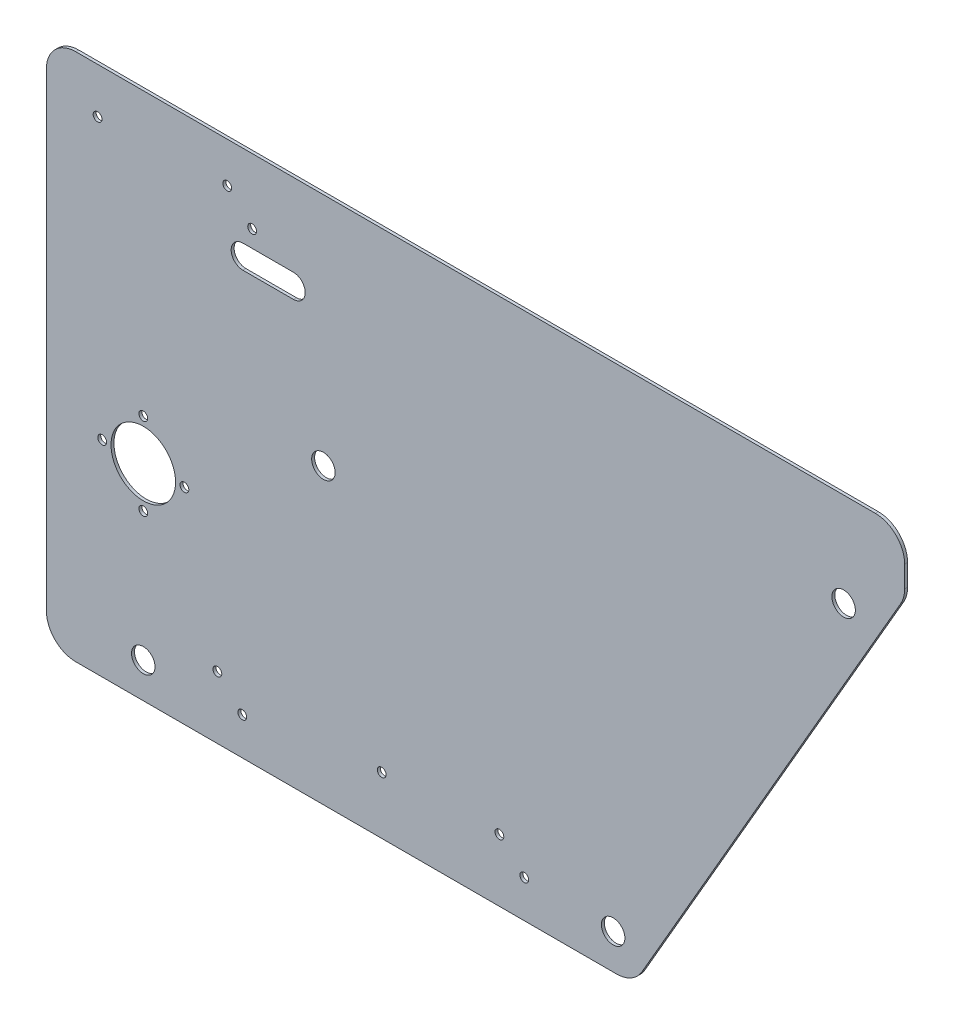
SolidWorks part; units mm, degrees
ref_plane "Front Plane" through (0, 0, 0) normal (0, 0, 1) x (1, 0, 0)
ref_plane "Top Plane" through (0, 0, 0) normal (0, 1, 0) x (1, 0, 0)
ref_plane "Right Plane" through (0, 0, 0) normal (1, 0, 0) x (0, 0, -1)
sketch "Sketch1" plane through (0, 0, 0) normal (0, 0, 1) x (1, 0, 0)
  line L0 (100, 80) -> (192.376, 80)
  line L1 (-100, -80) -> (100, -80)
  line L2 (-100, -80) -> (-100, 80)
  line L3 (-100, 80) -> (100, 80)
  line L4 (100, -80) -> (100, 80)
  line L5 (-100, -80) -> (100, 80) construction
  line L6 (-100, 80) -> (100, -80) construction
  line L7 (192.376, 80) -> (100, -80)
  line L8 (100, 80) -> (100, -80)
  line L10 (-100, 80) -> (192.376, 80)
  line L11 (-100, 80) -> (-100, 100)
  line L12 (-100, 100) -> (192.376, 100)
  line L13 (192.376, 80) -> (192.376, 100)
  point P0 (0, 0)
  dimension "D1" = 160
  dimension "D2" = 200
  dimension "D3" = 30
  dimension "D4" = 20
extrude "Boss-Extrude1" add sketch "Sketch1" along normal blind 1 contours L1 L4 L3 L2 | L7 L0 L4 | L11 L10 L13 L12 region at (0, 0, 0) region at (130.792, 26.6667, 0)
fillet "Fillet1" radius 10 5 edges at (100, -80, 0.5) (-100, -80, 0.5) (192.376, 100, 0.5) (-100, 100, 0.5) (192.376, 80, 0.5)
sketch "Sketch2" plane through (0, 0, 1) normal (0, 0, 1) x (1, 0, 0)
  line L0 (-90, -80) -> (94.2265, -80) construction
  line L1 (191.0363, 77.6795) -> (102.8868, -75) construction
  line L3 (-90, 100) -> (182.376, 100) construction
  line L4 (-33.0592, 68) -> (-15.8429, 68) construction
  line L7 (-100, -70) -> (-100, 90) construction
  line L9 (-33.0592, 72) -> (-15.8429, 72)
  line L10 (-33.0592, 64) -> (-15.8429, 64)
  circle A0 centre (93.0718, -68) radius 4
  circle A1 centre (171.5914, 68) radius 4
  circle A2 centre (-67, -10) radius 11
  circle A3 centre (-67, -68) radius 4
  circle A4 centre (-53, -10) radius 1.5
  circle A5 centre (-67, 4) radius 1.5
  circle A6 centre (-81, -10) radius 1.5
  circle A7 centre (-67, -24) radius 1.5
  circle A10 centre (-5.639, 20) radius 4
  arc A11 (-33.0592, 72) -> (-33.0592, 64) centre (-33.0592, 68) ccw
  arc A12 (-15.8429, 64) -> (-15.8429, 72) centre (-15.8429, 68) ccw
  circle A32 centre (62.7961, -67.2426) radius 1.5
  circle A33 centre (54.3108, -58.7574) radius 1.5
  circle A34 centre (-33.2742, -67.2426) radius 1.5
  circle A35 centre (-41.7595, -58.7574) radius 1.5
  circle A36 centre (14.2259, -60.5) radius 1.5
  circle A37 centre (-29.9152, 77.7574) radius 1.5
  circle A38 centre (-38.4005, 86.2426) radius 1.5
  circle A39 centre (-82.5763, 84.5) radius 1.5
  point P12 (-24.451, 68)
  point P36 (0, 0)
  point P38 (0, 0)
  point P39 (0, 0)
  point P42 (-5.639, 20)
  point P44 (0, 0)
  point P45 (0, 0)
  dimension "D3" = 8
  dimension "D4" = 8
  dimension "D9" = 22
  dimension "D10" = 8
  dimension "D12" = 3
  dimension "D13" = 3
  dimension "D14" = 3
  dimension "D15" = 3
  dimension "D16" = 14
  dimension "D20" = 4
  dimension "D22" = 8
  dimension "D23" = 3
  dimension "D1" = 12
  dimension "D2" = 12
  dimension "D5" = 32
  dimension "D6" = 12
  dimension "D7" = 33
  dimension "D8" = 70
  dimension "D11" = 12
  dimension "D17" = 14
  dimension "D18" = 14
  dimension "D19" = 14
  dimension "D21" = 80
extrude "Cut-Extrude1" cut sketch "Sketch2" against normal blind 3
